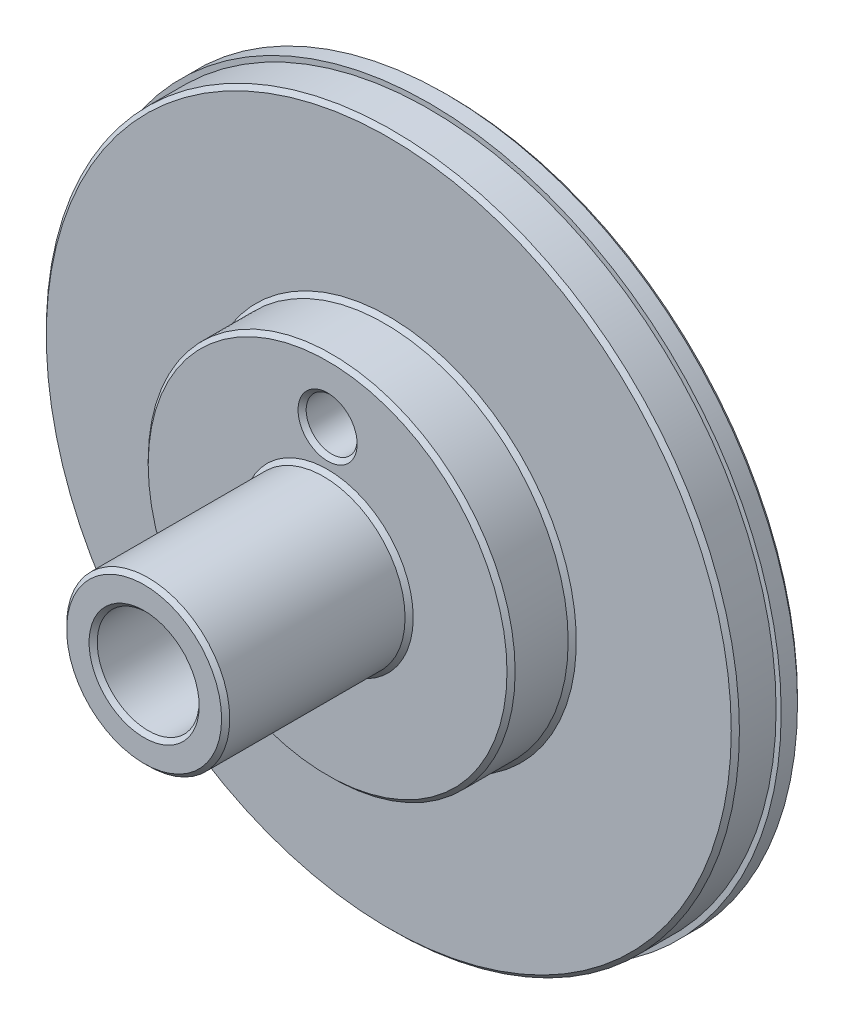
SolidWorks part; units mm, degrees
ref_plane "Front Plane" through (0, 0, 0) normal (0, 0, 1) x (1, 0, 0)
ref_plane "Top Plane" through (0, 0, 0) normal (0, 1, 0) x (1, 0, 0)
ref_plane "Right Plane" through (0, 0, 0) normal (1, 0, 0) x (0, 0, -1)
sketch "Sketch1" plane through (0, 0, 0) normal (0, 0, 1) x (1, 0, 0)
  circle A0 centre (0, 0) radius 17.25
  circle A1 centre (0, 0) radius 17
  circle A2 centre (0, 0) radius 9
  circle A3 centre (0, 0) radius 4
  dimension "D1" = 34.5
  dimension "D2" = 34
  dimension "D3" = 18
  dimension "D4" = 8
extrude "Boss-Extrude1" add sketch "Sketch1" along normal blind 1 contours A0 A1 region at (-17.2012, 0, 0)
extrude "Boss-Extrude2" add sketch "Sketch1<3>" along normal blind 3 contours A1 A2 region at (-16.5192, 0, 0)
sketch "Sketch1<3>" plane through (0, 0, 0) normal (0, 0, 1) x (1, 0, 0) same geometry as "Sketch1"
extrude "Boss-Extrude3" add sketch "Sketch1<4>" along normal blind 6 contours A2 A3 region at (-8.7454, 0, 0)
sketch "Sketch1<4>" plane through (0, 0, 0) normal (0, 0, 1) x (1, 0, 0) same geometry as "Sketch1"
extrude "Boss-Extrude4" add sketch "Sketch1<5>" along normal blind 15 contours A3 region at (0, 0, 0)
sketch "Sketch1<5>" plane through (0, 0, 0) normal (0, 0, 1) x (1, 0, 0) same geometry as "Sketch1"
sketch "Sketch2" plane through (0, 0, 15) normal (0, 0, 1) x (1, 0, 0)
  circle A0 centre (0, 0) radius 2.5
  dimension "D1" = 5
extrude "Cut-Extrude1" cut sketch "Sketch2" against normal up to surface (15 mm away) up to face at (17.25, 0, 0)
sketch "Sketch3" plane through (0, 0, 6) normal (0, 0, 1) x (1, 0, 0)
  circle A0 centre (0, 6) radius 1.25
  point P2 (0, 0)
  dimension "D2" = 2.5
  dimension "D1" = 6
extrude "Cut-Extrude2" cut sketch "Sketch3" against normal blind 6
chamfer "Chamfer1" distance 0.2 angle 45 10 edges at (17.25, 0, 0) (2.5, 0, 0) (1.25, 6, 0) (17, 0, 3) (9, 0, 3) (9, 0, 6) (4, 0, 6) (1.25, 6, 6) (4, 0, 15) (2.5, 0, 15)
